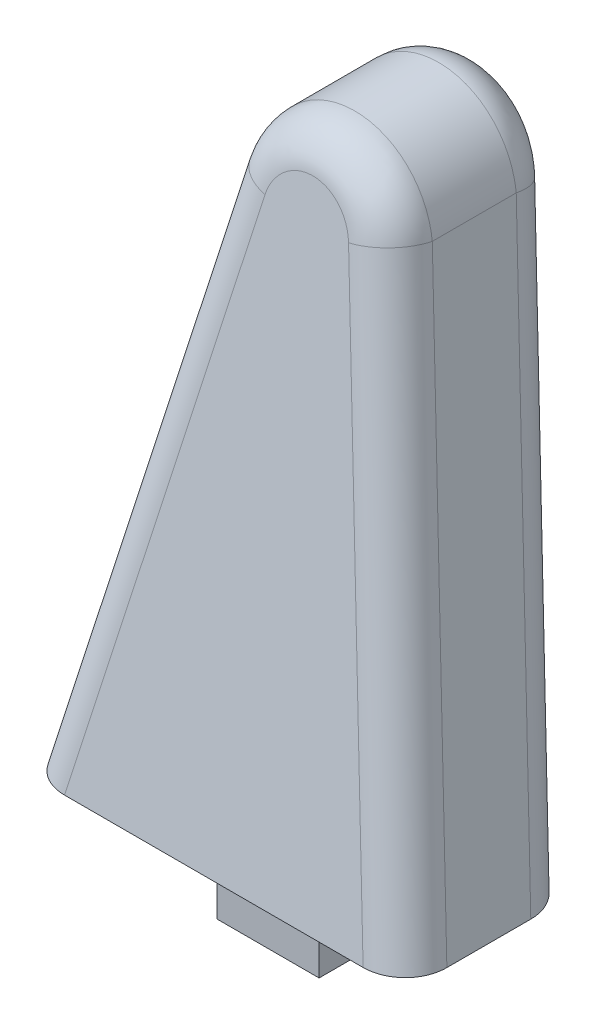
SolidWorks part; units mm, degrees
ref_plane "Front Plane" through (0, 0, 0) normal (0, 0, 1) x (1, 0, 0)
ref_plane "Top Plane" through (0, 0, 0) normal (0, 1, 0) x (1, 0, 0)
ref_plane "Right Plane" through (0, 0, 0) normal (1, 0, 0) x (0, 0, -1)
sketch "Sketch1" plane through (0, 0, 0) normal (0, 0, 1) x (1, 0, 0)
  line L0 (29.78, 157) -> (52.22, 157)
  line L1 (52.22, 157) -> (45.8992, 187.999)
  line L2 (36.1008, 187.999) -> (29.78, 157)
  arc A0 (45.8992, 187.999) -> (36.1008, 187.999) centre (41, 187) ccw
extrude "Boss-Extrude1" add sketch "Sketch1" along normal blind 20 from offset 47
sketch "Sketch2" plane through (0, 0, 0) normal (1, 0, 0) x (0, 0, -1)
  line L0 (-67.4106, 150) -> (-81, 150)
  line L1 (-81, 150) -> (-81, 200)
  line L2 (-81, 200) -> (-58.5943, 200)
  line L3 (-58.5943, 200) -> (-67.4106, 150)
extrude "Boss-Extrude2" add sketch "Sketch2" along normal blind 30 from offset 26 separate body
combine bodies "Combine1" operation type subtract main body 101 bodies to subtract 102
sketch "Sketch3" plane through (0, 0, 0) normal (1, 0, 0) x (0, 0, -1)
  line L0 (-57.4106, 150) -> (-48.5943, 200)
  line L1 (-48.5943, 200) -> (-36, 200)
  line L2 (-36, 200) -> (-36, 150)
  line L3 (-36, 150) -> (-57.4106, 150)
extrude "Boss-Extrude3" add sketch "Sketch3" along normal blind 30 from offset 26 separate body
combine bodies "Combine2" operation type subtract main body 103 bodies to subtract 104
fillet "Fillet1" radius 2.5 3 edges at (32.9404, 172.4995, 63.4434) (41, 192, 60.0049) (49.0596, 172.4995, 63.4434)
fillet "Fillet2" radius 2.5 3 edges at (32.9404, 172.4995, 53.4434) (41, 192, 50.0049) (49.0596, 172.4995, 53.4434)
sketch "Sketch4" plane through (0, 0, 0) normal (0, 0, 1) x (1, 0, 0)
  line L1 (38, 152) -> (44, 152)
  line L2 (38, 152) -> (38, 157.01)
  line L3 (38, 157.01) -> (44, 157.01)
  line L4 (44, 152) -> (44, 157.01)
extrude "Boss-Extrude4" add sketch "Sketch4" along normal blind 4 from offset 59
sketch "Sketch5" plane through (0, 0, 0) normal (0, 1, 0) x (1, 0, 0)
  circle A0 centre (47.5, -61) radius 1
extrude "Boss-Extrude5" add sketch "Sketch5" along normal blind 7.1 from offset 156.9 separate body
combine bodies "Combine3" operation type subtract main body 106 bodies to subtract 107
